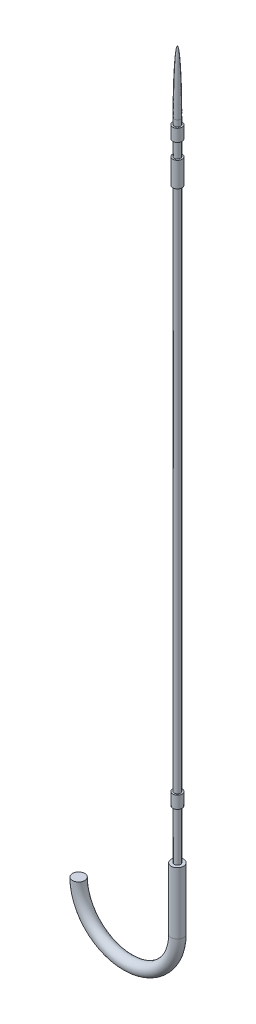
SolidWorks part; units mm, degrees
ref_plane "Alzado" through (0, 0, 0) normal (0, 0, 1) x (1, 0, 0)
ref_plane "Planta" through (0, 0, 0) normal (0, 1, 0) x (1, 0, 0)
ref_plane "Vista lateral" through (0, 0, 0) normal (1, 0, 0) x (0, 0, -1)
sketch "Croquis3" plane through (0, 0, 0) normal (0, 1, 0) x (1, 0, 0)
  circle A0 centre (0, 0) radius 5
  dimension "D1" = 10
extrude "Saliente-Extruir1" add sketch "Croquis3" along normal blind 870
sketch "Croquis5" plane through (0, 0, 0) normal (0, -1, 0) x (1, 0, 0)
  circle A0 centre (0, 0) radius 7.5
  dimension "D1" = 15
extrude "Saliente-Extruir2" add sketch "Croquis5" along normal blind 20
sketch "Croquis6" plane through (0, -20, 0) normal (0, -1, 0) x (1, 0, 0)
  circle A0 centre (0, 0) radius 5
  dimension "D1" = 10
extrude "Saliente-Extruir3" add sketch "Croquis6" along normal blind 80
sketch "Croquis7" plane through (0, 0, 0) normal (0, 0, 1) x (1, 0, 0)
  line L0 (0, -100) -> (0, -200)
  line L1 (-5, -100) -> (5, -100) construction
  arc A0 (0, -200) -> (-160, -200) centre (-80, -200) cw
  dimension "D1" = 100
  dimension "D2" = 80
sketch "Croquis8" plane through (0, -100, 0) normal (0, -1, 0) x (1, 0, 0)
  circle A0 centre (0, 0) radius 10
  dimension "D1" = 20
sweep "Barrer1" add profiles "Croquis8" path "Croquis7"
sketch "Croquis9" plane through (0, 870, 0) normal (0, 1, 0) x (1, 0, 0)
  circle A0 centre (0, 0) radius 7.5
  dimension "D1" = 15
extrude "Saliente-Extruir4" add sketch "Croquis9" along normal blind 20 and the other way blind 20
sketch "Croquis10" plane through (0, 890, 0) normal (0, 1, 0) x (1, 0, 0)
  circle A0 centre (0, 0) radius 5
  dimension "D1" = 10
extrude "Saliente-Extruir5" add sketch "Croquis10" along normal blind 25
sketch "Croquis11" plane through (0, 915, 0) normal (0, 1, 0) x (1, 0, 0)
  circle A0 centre (0, 0) radius 7.5
  dimension "D1" = 15
extrude "Saliente-Extruir6" add sketch "Croquis11" along normal blind 20
sketch "Croquis12" plane through (0, 935, 0) normal (0, 1, 0) x (1, 0, 0)
  circle A0 centre (0, 0) radius 5
  dimension "D1" = 10
extrude "Saliente-Extruir7" add sketch "Croquis12" along normal blind 10
dome "Cúpula2" faces to dome 1 distance 100 reverse direction no elliptical dome yes face at (0, 945, 5) parameters "D1"=100
